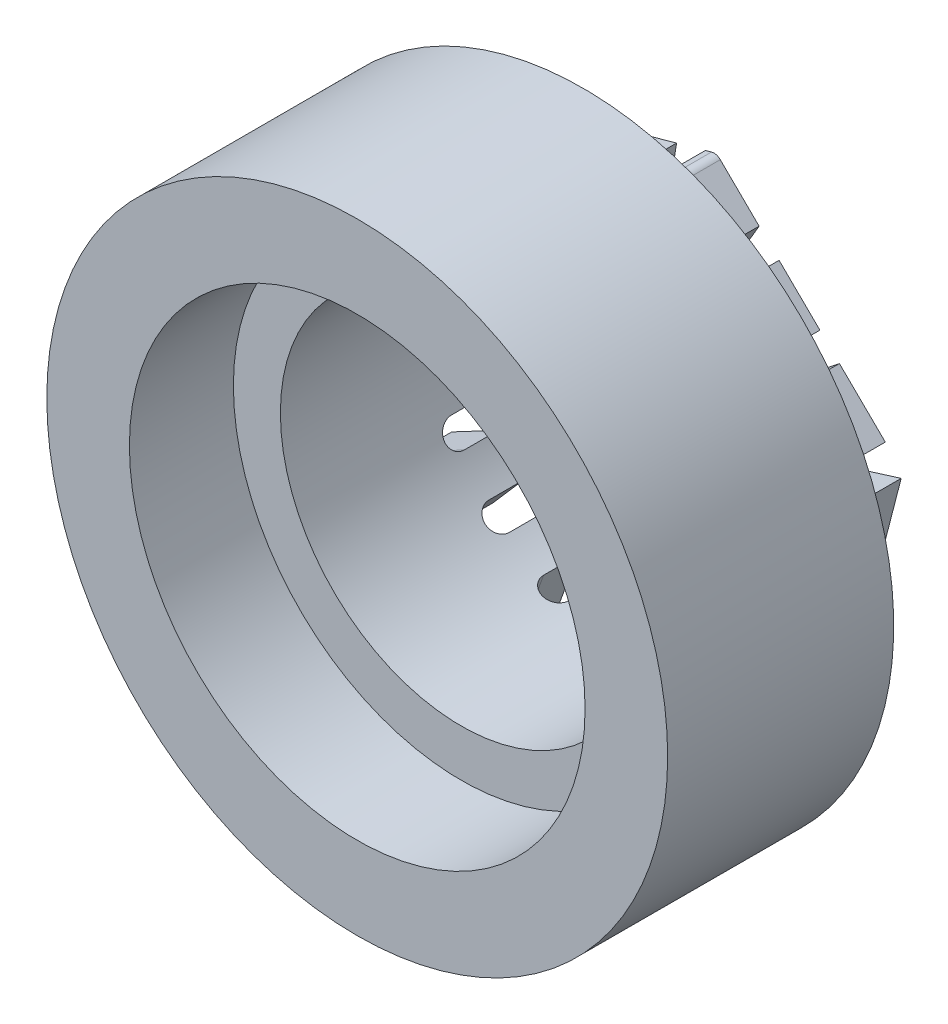
SolidWorks part; units mm, degrees
material "AISI Type 316L stainless steel"
ref_plane "Front Plane" through (0, 0, 0) normal (0, 0, 1) x (1, 0, 0)
ref_plane "Top Plane" through (0, 0, 0) normal (0, 1, 0) x (1, 0, 0)
ref_plane "Right Plane" through (0, 0, 0) normal (1, 0, 0) x (0, 0, -1)
sketch "Sketch1" plane through (0, 0, 0) normal (0, 0, 1) x (1, 0, 0)
  circle A0 centre (0, 0) radius 21.7995
  dimension "D1" = 43.5991
extrude "Boss-Extrude1" add sketch "Sketch1" along normal blind 20.6502
sketch "Sketch2" plane through (0, 0, 20.6502) normal (0, 0, 1) x (1, 0, 0)
  circle A0 centre (0, 0) radius 12.7
  dimension "D1" = 25.4
extrude "Cut-Extrude1" cut sketch "Sketch2" against normal blind 20.6502
sketch "Sketch3" plane through (0, 0, 20.6502) normal (0, 0, 1) x (1, 0, 0)
  circle A0 centre (0, 0) radius 16
  dimension "D1" = 32
extrude "Cut-Extrude2" cut sketch "Sketch3" against normal blind 7.3025
sketch "Sketch4" plane through (0, 0, 0) normal (0, 0, -1) x (-1, 0, 0)
  line L1 (17.6618, -4.9073) -> (13.0808, 12.8419)
  line L2 (13.0808, 12.8419) -> (-4.581, 17.7492)
  line L3 (-4.581, 17.7492) -> (-17.6618, 4.9073)
  line L4 (-17.6618, 4.9073) -> (-13.0808, -12.8419)
  line L5 (-13.0808, -12.8419) -> (4.581, -17.7492)
  line L6 (4.581, -17.7492) -> (17.6618, -4.9073)
  circle A1 centre (0, 0) radius 15.875 construction
  dimension "D1" = 31.75
extrude "Cut-Extrude3" cut sketch "Sketch4" against normal blind 4.7752 flip side to cut
sketch "Sketch5" plane through (-15.3713, 3.9673, 0) normal (-0.9683, 0.2499, 0) x (0, 0, 1)
  line L0 (0, 0) -> (4.7752, 0) construction
  line L1 (4.7752, -9.1654) -> (4.7752, 9.1654) construction
  line L2 (2.3876, 0.9525) -> (0, 0.9525)
  line L3 (0, -9.1654) -> (0, 9.1654) construction
  line L4 (0, 0.9525) -> (0, -0.9525)
  line L5 (0, -0.9525) -> (2.3876, -0.9525)
  arc A1 (2.3876, 0.9525) -> (2.3876, -0.9525) centre (2.3876, 0) cw
extrude "Cut-Extrude4" cut sketch "Sketch5" against normal blind 9.8552 and the other way blind 9.8552
pattern_circular "CirPattern1" count 17 over 360 about axis through (0, 0, 13.3477) along (0, 0, 1) of "Cut-Extrude4" reverse direction yes
fillet "Fillet1" radius 0.635 6 edges at (-17.6618, -4.9073, 2.3876) (-13.0808, 12.8419, 2.3876) (4.581, 17.7492, 2.3876) (17.6618, 4.9073, 3.965) (13.0808, -12.8419, 3.965) (-4.581, -17.7492, 2.3876)
sketch "Sketch10" plane through (0, 0, 0) normal (1, 0, 0) x (0, 0, -1)
  line L0 (-20.6502, 21.7995) -> (-20.6502, 18.8998) construction
  line L1 (-20.6502, 21.7995) -> (-20.6502, -21.7995) construction
  line L2 (-20.6502, 18.8998) -> (-4.7752, 18.8998) construction
  line L3 (-4.7752, -21.7995) -> (-4.7752, 21.7995) construction
  line L4 (-20.6502, 21.7995) -> (-4.7752, 21.7995)
  arc A0 (-4.7752, 21.7995) -> (-20.6502, 21.7995) centre (-12.7127, 31.2132) cw
  dimension "D1" = 2.8998
ref_axis "Axis1" through (0, 0, 13.3477) along (0, 0, 1)
revolve "Cut-Revolve1" [suppressed] cut sketch "Sketch10" angle 360 about axis through (0, 0, 13.3477) along (0, 0, 1)
